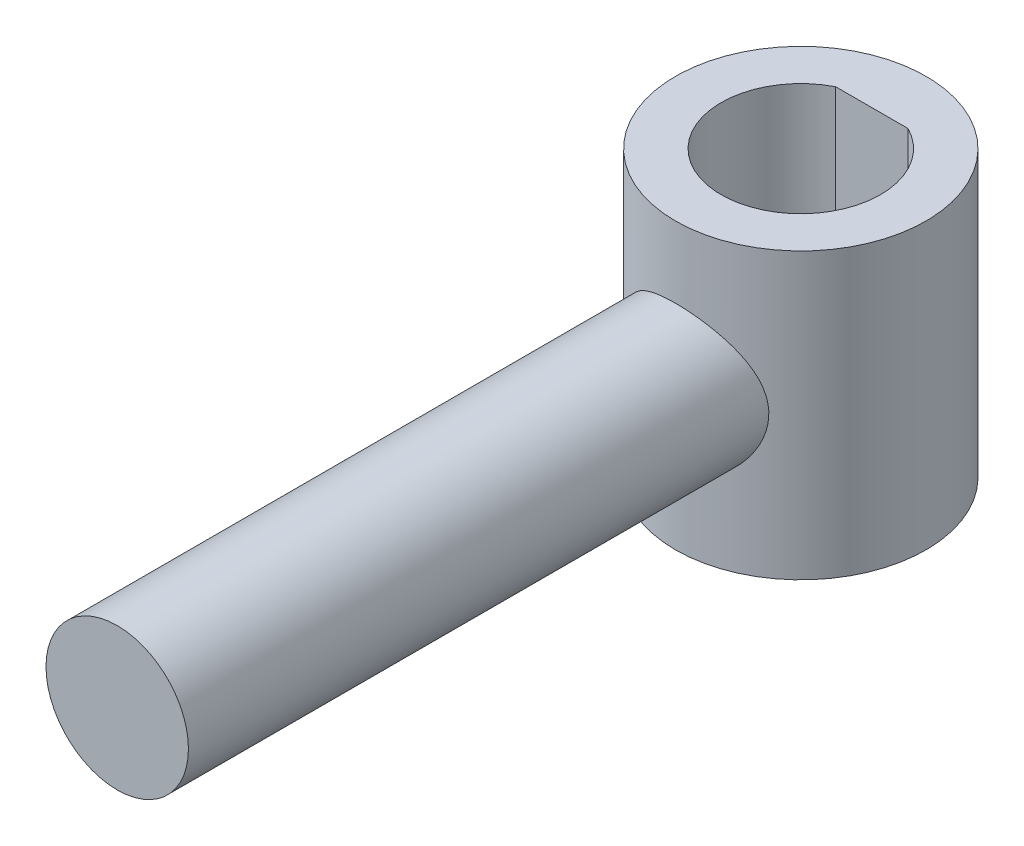
SolidWorks part; units mm, degrees
material "ABS"
ref_plane "Front Plane" through (0, 0, 0) normal (0, 0, 1) x (1, 0, 0)
ref_plane "Top Plane" through (0, 0, 0) normal (0, 1, 0) x (1, 0, 0)
ref_plane "Right Plane" through (0, 0, 0) normal (1, 0, 0) x (0, 0, -1)
sketch "Sketch1" plane through (0, 0, 0) normal (0, 1, 0) x (1, 0, 0)
  line L0 (3.175, 6.2385) -> (-3.175, 6.2385)
  arc A0 (-3.175, 6.2385) -> (3.175, 6.2385) centre (0, 0) ccw
  circle A1 centre (0, 0) radius 11
  dimension "D1" = 14
  dimension "D2" = 4
  dimension "D3" = 6.35
sketch "Sketch2" plane through (0, 0, 0) normal (0, 0, 1) x (1, 0, 0)
  circle A0 centre (0, 0) radius 6.25
  dimension "D1" = 12.5
extrude "Boss-Extrude3" add sketch "Sketch2" along normal blind 60 contours A0
extrude "Boss-Extrude4" add sketch "Sketch1" along normal mid plane 25 contours A1
extrude "Cut-Extrude1" cut sketch "Sketch1<4>" against normal through all both and the other way through all contours A0 L0
sketch "Sketch1<4>" plane through (0, 0, 0) normal (0, 1, 0) x (1, 0, 0) same geometry as "Sketch1"
ref_plane "Plane1" through (0, 0, 54) normal (0, 0, 1) x (1, 0, 0)
sketch "Sketch3" plane through (0, 0, 54) normal (0, 0, 1) x (1, 0, 0)
  line L0 (-3.175, -5.3835) -> (3.175, -5.3835)
  circle A2 centre (0, 0) radius 6.25 construction
  arc A3 (3.175, -5.3835) -> (-3.175, -5.3835) centre (0, 0) cw
  point P3 (0, -5.3835)
  dimension "D1" = 6.35
extrude "Cut-Extrude2" cut sketch "Sketch3" against normal mid plane 4.7
